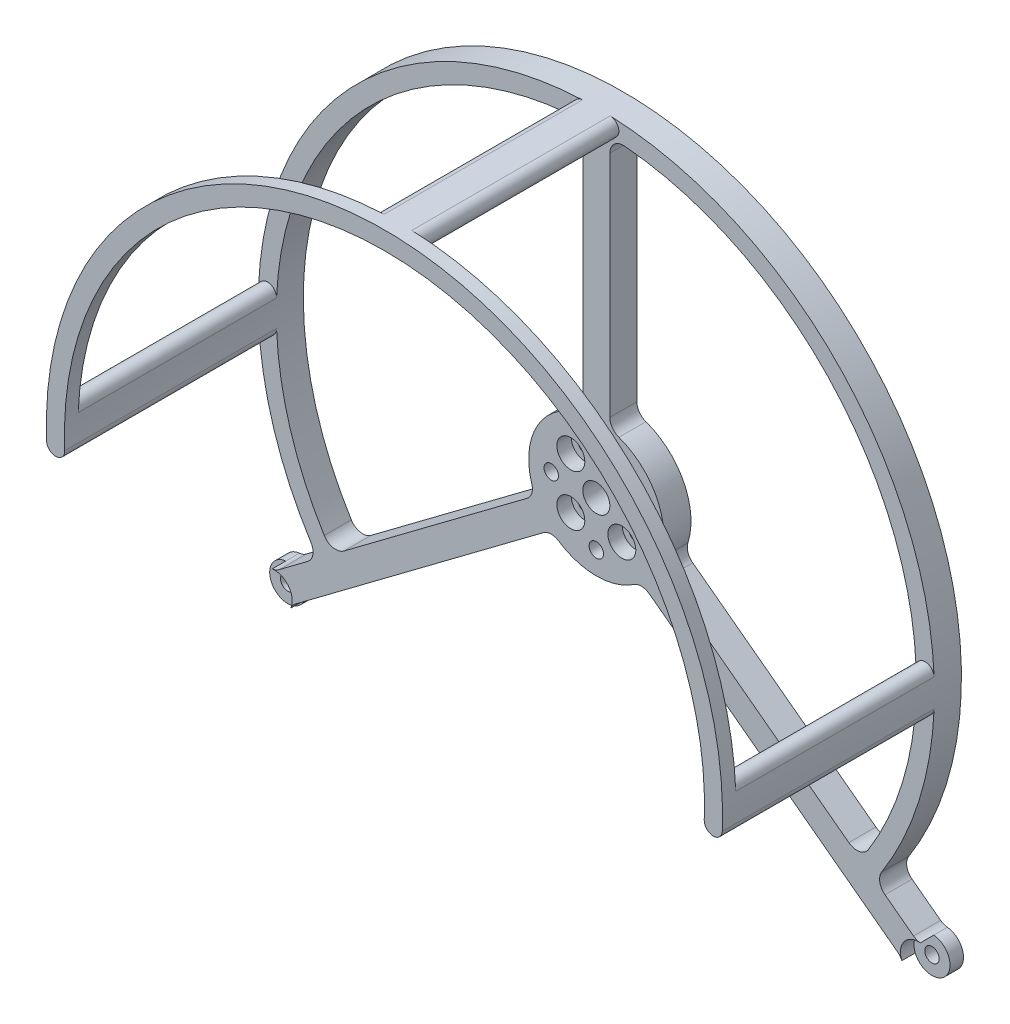
SolidWorks part; units mm, degrees
ref_plane "前视基准面" through (0, 0, 0) normal (0, 0, 1) x (1, 0, 0)
ref_plane "上视基准面" through (0, 0, 0) normal (0, 1, 0) x (1, 0, 0)
ref_plane "右视基准面" through (0, 0, 0) normal (1, 0, 0) x (0, 0, -1)
sketch "草图1" plane through (0, 0, 0) normal (0, 0, 1) x (1, 0, 0)
  line L0 (0, 0) -> (10, 0) construction
  line L1 (0, 0) -> (0, -10) construction
  line L2 (0, 0) -> (5.6569, -5.6569) construction
  circle A0 centre (0, 0) radius 15
  circle A1 centre (0, 0) radius 8 construction
  circle A2 centre (0, 0) radius 10 construction
  circle A3 centre (5.6569, -5.6569) radius 1.6
  circle A4 centre (-5.6569, -5.6569) radius 1.6
  circle A5 centre (5.6569, 5.6569) radius 1.6
  circle A6 centre (-5.6569, 5.6569) radius 1.6
  circle A7 centre (0, -10) radius 1.6
  circle A8 centre (10, 0) radius 1.6
  circle A9 centre (-10, 0) radius 1.6
  circle A10 centre (0, 10) radius 1.6
  dimension "D1" = 30
  dimension "D2" = 16
  dimension "D3" = 20
  dimension "D5" = 3.2
  dimension "D6" = 3.2
extrude "凸台-拉伸1" add sketch "草图1" along normal blind 6
sketch "草图2" plane through (0, 0, 6) normal (0, 0, 1) x (1, 0, 0)
  line L0 (0, 0) -> (8, 0) construction
  line L1 (0, 0) -> (0, -8) construction
  circle A0 centre (0, 0) radius 8 construction
  circle A1 centre (5.6569, 5.6569) radius 3.1
  circle A2 centre (5.6569, -5.6569) radius 3.1
  circle A3 centre (-5.6569, -5.6569) radius 3.1
  circle A4 centre (-5.6569, 5.6569) radius 3.1
  dimension "D1" = 6.2
extrude "切除-拉伸1" cut sketch "草图2" against normal blind 3.2
sketch "草图4" plane through (0, 0, 0) normal (0, 0, -1) x (-1, 0, 0)
  circle A0 centre (0, 0) radius 3
  dimension "D1" = 6
extrude "切除-拉伸2" cut sketch "草图4" against normal blind 8
sketch "草图3" plane through (0, 0, 0) normal (0, 0, -1) x (-1, 0, 0)
  line L0 (0, 0) -> (15, 0) construction
  line L1 (0, 0) -> (55.2216, -41.3712) construction
  line L5 (13.5609, -6.4111) -> (76.4213, -53.5052)
  line L9 (9.9634, -11.213) -> (72.8238, -58.3071)
  line L10 (76.4213, -53.5052) -> (72.8238, -58.3071)
  circle A0 centre (0, 0) radius 66 construction
  circle A1 centre (0, 0) radius 69 construction
  circle A3 centre (0, 0) radius 15 construction
  circle A4 centre (0, 0) radius 15
  circle M4 centre (0, 0) radius 15
  dimension "D1" = 132
  dimension "D2" = 138
  dimension "D3" = 30
  dimension "D5" = 93.29
  dimension "D4" = 3
  dimension "D6" = 36.84
extrude "凸台-拉伸3" add sketch "草图3" against normal blind 6 contours L10 L5 L9 M4 region at (-43.2733, -32.4197, 0)
sketch "草图5" plane through (0, 0, 0) normal (0, 0, -1) x (-1, 0, 0)
  line L0 (0, 0) -> (74.6226, -55.9061) construction
  line L1 (76.4213, -53.5052) -> (72.8238, -58.3071) construction
  circle A0 centre (71.4599, -53.5367) radius 1.6
  circle A1 centre (0, 0) radius 3 construction
  dimension "D1" = 3.2
  dimension "D2" = 89.29
extrude "切除-拉伸3" cut sketch "草图5" against normal blind 6
mirror "镜向2" about plane through (0, 0, 0) normal (1, 0, 0) of "切除-拉伸3", "凸台-拉伸3"
sketch "草图6" plane through (0, 0, 0) normal (0, 0, -1) x (-1, 0, 0)
  circle A0 centre (-71.4599, -53.5367) radius 4
  circle A1 centre (-71.4599, -53.5367) radius 1.6
  circle A2 centre (71.4599, -53.5367) radius 1.6
  circle A3 centre (71.4599, -53.5367) radius 4
  dimension "D1" = 8
  dimension "D2" = 3.2
  dimension "D3" = 8
  dimension "D4" = 3.2
extrude "凸台-拉伸4" add sketch "草图6" against normal blind 6
sketch "草图7" plane through (0, 0, 0) normal (0, 0, -1) x (-1, 0, 0)
  line L0 (-75.3761, -52.7221) -> (-79.5868, -53.5367)
  line L1 (-79.5868, -53.5367) -> (-72.314, -61.4299)
  line L2 (-72.314, -61.4299) -> (-71.8903, -57.5135)
  line L3 (71.7786, -57.524) -> (73.2525, -62.4618)
  line L4 (73.2525, -62.4618) -> (79.8511, -53.0431)
  line L5 (79.8511, -53.0431) -> (75.3761, -52.7221)
  arc A0 (-75.3761, -52.7221) -> (-71.8903, -57.5135) centre (-71.4599, -53.5367) ccw
  arc A1 (71.7786, -57.524) -> (75.3761, -52.7221) centre (71.4599, -53.5367) ccw
extrude "切除-拉伸4" cut sketch "草图7" against normal blind 6 contours A1 L5 L4 L3 | A0 L2 L1 L0
sketch "草图8" plane through (0, 0, 0) normal (0, 0, -1) x (-1, 0, 0)
  line L0 (-58.5702, -40.1314) -> (-61.7742, -42.5318)
  line L1 (-13.5609, -6.4111) -> (-71.1413, -49.5494) construction
  line L2 (61.7742, -42.5318) -> (58.5702, -40.1314)
  line L3 (13.5609, -6.4111) -> (71.1413, -49.5494) construction
  circle A0 centre (0, 0) radius 89.29 construction
  arc A1 (61.7742, -42.5318) -> (-61.7742, -42.5318) centre (0, 0) ccw
  arc A2 (58.5702, -40.1314) -> (-58.5702, -40.1314) centre (0, 0) ccw
  dimension "D1" = 150
  dimension "D2" = 142
extrude "凸台-拉伸5" add sketch "草图8" against normal blind 6
sketch "草图9" plane through (0, 0, 0) normal (0, 0, -1) x (-1, 0, 0)
  line L0 (0, 0) -> (0, 71) construction
  line L1 (-3, 14.6969) -> (-3, 70.9366)
  line L2 (3, 14.6969) -> (3, 70.9366)
  arc A0 (58.5702, -40.1314) -> (-58.5702, -40.1314) centre (0, 0) ccw construction
  arc A1 (13.5609, -6.4111) -> (-13.5609, -6.4111) centre (0, 0) ccw construction
  arc A2 (3, 14.6969) -> (-3, 14.6969) centre (0, 0) ccw
  arc A3 (3, 70.9366) -> (-3, 70.9366) centre (0, 0) ccw
  dimension "D1" = 3
extrude "凸台-拉伸6" add sketch "草图9" against normal blind 6
sketch "草图10" plane through (0, 0, 6) normal (0, 0, 1) x (1, 0, 0)
  line L0 (0, 0) -> (-73, 0) construction
  line L1 (-73, 0) -> (-75, 0) construction
  arc A0 (-72.8288, 4.997) -> (-72.8288, -4.997) centre (0, 0) ccw construction
  arc A1 (-74.9366, 3.0822) -> (-74.9366, -3.0822) centre (0, 0) ccw
  arc A10 (-70.94, 2.9178) -> (-70.94, -2.9178) centre (0, 0) ccw
  arc A11 (-70.94, 2.9178) -> (-74.9366, 3.0822) centre (-72.9383, 3) ccw
  arc A12 (-70.94, -2.9178) -> (-74.9366, -3.0822) centre (-72.9383, -3) cw
  arc A13 (2.9178, 70.94) -> (-2.9178, 70.94) centre (0, 0) ccw
  arc A14 (-2.9178, 70.94) -> (-3.0822, 74.9366) centre (-3, 72.9383) cw
  arc A15 (3.0822, 74.9366) -> (-3.0822, 74.9366) centre (0, 0) ccw
  arc A16 (2.9178, 70.94) -> (3.0822, 74.9366) centre (3, 72.9383) ccw
  arc A17 (70.94, -2.9178) -> (70.94, 2.9178) centre (0, 0) ccw
  arc A18 (70.94, 2.9178) -> (74.9366, 3.0822) centre (72.9383, 3) cw
  arc A19 (74.9366, -3.0822) -> (74.9366, 3.0822) centre (0, 0) ccw
  arc A20 (70.94, -2.9178) -> (74.9366, -3.0822) centre (72.9383, -3) ccw
  arc A25 (-2.9178, -70.94) -> (2.9178, -70.94) centre (0, 0) ccw [skipped]
  arc A26 (2.9178, -70.94) -> (3.0822, -74.9366) centre (3, -72.9383) cw [skipped]
  arc A27 (-3.0822, -74.9366) -> (3.0822, -74.9366) centre (0, 0) ccw [skipped]
  arc A28 (-2.9178, -70.94) -> (-3.0822, -74.9366) centre (-3, -72.9383) ccw [skipped]
  point P33 (0, 0)
  dimension "D1" = 146
  dimension "D2" = 3
  dimension "D3" = 71
  dimension "D4" = 75
  dimension "D5" = 2
  dimension "D6" = 73
  dimension "D7" = 4
extrude "凸台-拉伸7" add sketch "草图10" along normal blind 44
sketch "草图11" plane through (0, 0, 50) normal (0, 0, 1) x (1, 0, 0)
  arc A0 (70.94, -2.9178) -> (-70.94, -2.9178) centre (0, 0) ccw
  arc A1 (74.9366, -3.0822) -> (-74.9366, -3.0822) centre (0, 0) ccw
  arc A2 (70.94, -2.9178) -> (74.9366, -3.0822) centre (72.9383, -3) ccw
  arc A3 (-74.9366, -3.0822) -> (-70.94, -2.9178) centre (-72.9383, -3) ccw
  dimension "D1" = 75
  dimension "D2" = 2
  dimension "D3" = 2
extrude "凸台-拉伸8" add sketch "草图11" along normal blind 3
fillet "圆角5" radius 3 14 edges at (-58.5702, -40.1314, 3) (-13.5609, -6.4111, 3) (-3, 14.6969, 3) (3, 14.6969, 3) (13.5609, -6.4111, 3) (58.5702, -40.1314, 3) (61.7742, -42.5318, 3) (71.1413, -49.5494, 3) (67.5438, -54.3513, 3) (9.9634, -11.213, 3) (-9.9634, -11.213, 3) (-71.1413, -49.5494, 3) (-67.5438, -54.3513, 3) (-61.7742, -42.5318, 3)
sketch "草图12" plane through (0, 0, 6) normal (0, 0, 1) x (1, 0, 0)
  line L0 (74.5576, -56.0674) -> (72.1117, -59.0614)
  line L1 (72.1117, -59.0614) -> (69.5336, -58.7202)
  line L2 (69.5336, -58.7202) -> (69.7416, -57.1488)
  arc A0 (69.7416, -57.1488) -> (74.5576, -56.0674) centre (71.4599, -53.5367) ccw
extrude "切除-拉伸5" cut sketch "草图12" against normal blind 40 contours A0 L0 L1 L2
fillet "圆角6" radius 3 2 edges at (3, 70.9366, 3) (-3, 70.9366, 3)
sketch "草图13" plane through (0, 0, 6) normal (0, 0, 1) x (1, 0, 0)
  circle A0 centre (-71.4599, -53.5367) radius 4
  circle A1 centre (71.4599, -53.5367) radius 4
  dimension "D1" = 8
  dimension "D2" = 8
extrude "切除-拉伸6" cut sketch "草图13" against normal blind 3
